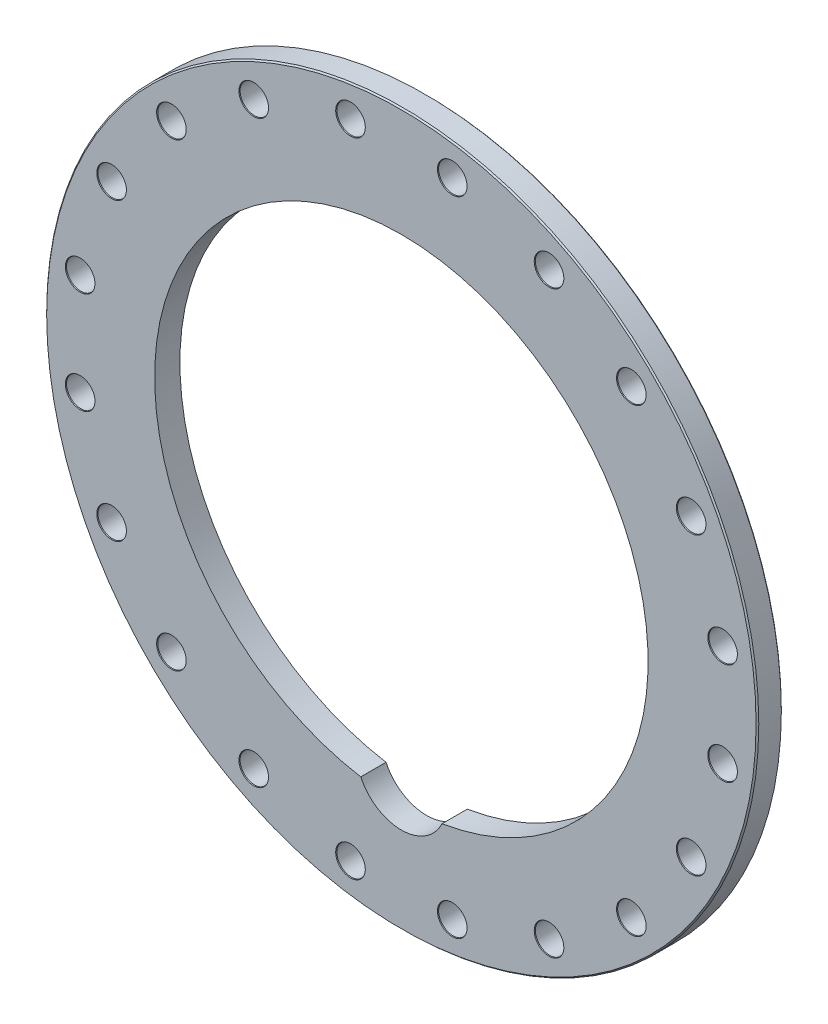
SolidWorks part; units mm, degrees
ref_plane "front" through (0, 0, 0) normal (0, 0, 1) x (1, 0, 0)
ref_plane "top" through (0, 0, 0) normal (0, 1, 0) x (1, 0, 0)
ref_plane "right" through (0, 0, 0) normal (1, 0, 0) x (0, 0, -1)
ref_axis "Axis1" through (0, 0, -80.9) along (0, 0, 1)
sketch "Sketch1" plane through (0, 0, 0) normal (0, 0, 1) x (1, 0, 0)
  circle A0 centre (0, 0) radius 201.6125
  arc A1 (22.9919, -137.795) -> (-22.9919, -137.795) centre (0, 0) ccw
  arc A2 (-22.9919, -137.795) -> (22.9919, -137.795) centre (0, -127) ccw
  point P3 (0, -152.4)
  dimension "D1" = 403.225
  dimension "D2" = 279.4
  dimension "D3" = 25.4
  dimension "D4" = 152.4
extrude "Base-Extrude" add sketch "Sketch1" along normal blind 15.875
sketch "align" plane through (0, 0, 0) normal (0, 0, 1) x (1, 0, 0)
  line L0 (0, 0) -> (104.6752, 0) construction
  line L1 (0, 0) -> (108.9551, 17.2568) construction
  dimension "D1" = 9
sketch "Sketch7" plane through (0, 0, 0) normal (1, 0, 0) x (0, 0, -1)
  line L0 (-14.3002, 214.0878) -> (-14.3002, -214.539)
  dimension "D1" = 14.3002
extrude "Cut-Extrude1" cut sketch "Sketch7" against normal through all and the other way through all flip side to cut
sketch "Sketch8" plane through (0, 0, 14.3002) normal (0, 0, 1) x (1, 0, 0)
  line L0 (0, 0) -> (120.4863, 19.0832) construction
  line L1 (0, 0) -> (115.3169, 0) construction
  point P0 (181.8828, 28.8074)
  dimension "D1" = 9
  dimension "D2" = 184.15
hole_wizard "5/8 (0.625) Diameter Hole1" positions "3DSketch1" profile "Sketch9" hole size "5/8" standard "Ansi Inch" end condition through all
sketch3d "3DSketch1"
  point P0 (181.8828, 28.8074, 14.3002)
sketch "Sketch9" plane through (181.8828, 28.8074, 14.3002) normal (1, 0, 0) x (0, -1, 0)
  line L0 (0, 0) -> (0, 14.3002)
  line L1 (0, 14.3002) -> (8.382, 14.3002)
  line L2 (8.1915, 13.8403) -> (8.1915, 0.4599)
  line L3 (8.1915, 0.4599) -> (8.382, 0)
  line L5 (8.382, 0) -> (0, 0)
  line L6 (-8.1915, 0.4599) -> (-8.382, 0) construction
  line L7 (8.382, 14.3002) -> (8.1915, 13.8403)
  line L8 (-8.382, 14.3002) -> (-8.1915, 13.8403) construction
  line L11 (0, -6.35) -> (0, 107.95) construction
  dimension "Thru Hole Dia." = 16.383
  dimension "Thru Hole Depth" = 14.3002
  dimension "Near C'Sink Dia." = 16.764
  dimension "Near C'Sink Angle" = 45
  dimension "Far C'Sink Dia." = 16.764
  dimension "Far C'Sink Angle" = 45
pattern_circular "CirPattern1" count 20 over 360 about axis through (0, 0, -80.9) along (0, 0, 1) of "5/8 (0.625) Diameter Hole1"
chamfer "Chamfer1" distance 0.762 angle 45 2 edges at (201.6125, 0, 0) (0, 201.6125, 14.3002)
sketch "L2D-00 Washer weld clearance." [suppressed] plane through (0, 0, 0) normal (0, 0, -1) x (-1, 0, 0)
  circle A0 centre (-181.8828, 25.0074) radius 13.4938
  circle A1 centre (0, 0) radius 168.275
  dimension "D1" = 336.55
  dimension "D2" = 26.9875
sketch "Sketch10" plane through (0, 0, 14.3002) normal (0, 0, 1) x (1, 0, 0)
  circle A0 centre (0, 0) radius 138.1193
